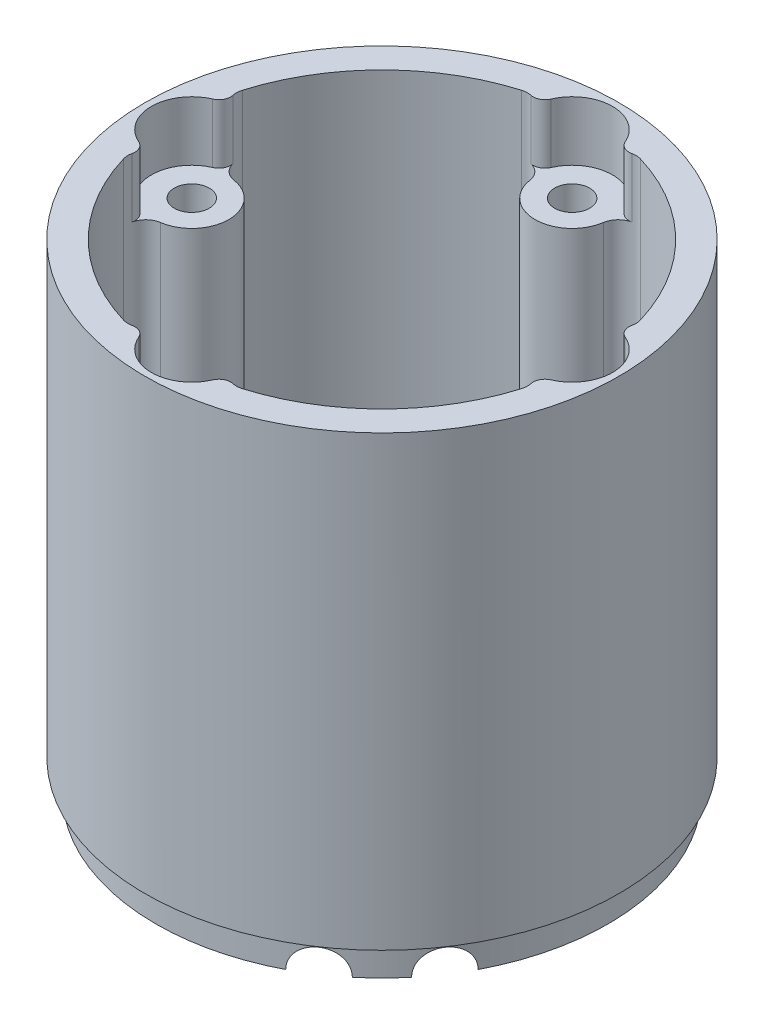
SolidWorks part; units mm, degrees
material "ABS"
ref_plane "Front Plane" through (0, 0, 0) normal (0, 0, 1) x (1, 0, 0)
ref_plane "Top Plane" through (0, 0, 0) normal (0, 1, 0) x (1, 0, 0)
ref_plane "Right Plane" through (0, 0, 0) normal (1, 0, 0) x (0, 0, -1)
sketch "Sketch1" plane through (0, 0, 0) normal (0, 0, 1) x (1, 0, 0)
  line L0 (0, 138.9318) -> (0, -74.0157) construction
  line L1 (44.45, 0) -> (44.45, 204.47)
  line L2 (44.45, 204.47) -> (50.7238, 204.47)
  line L3 (50.7238, 204.47) -> (50.7238, 108.585)
  line L4 (50.7238, 108.585) -> (52.832, 108.585)
  line L5 (52.832, 108.585) -> (52.832, 95.885)
  line L6 (52.832, 95.885) -> (50.7238, 95.885)
  line L7 (50.7238, 95.885) -> (50.7238, 0)
  line L8 (50.7238, 0) -> (44.45, 0)
  dimension "D1" = 88.9
  dimension "D2" = 204.47
  dimension "D3" = 12.7
  dimension "D4" = 101.4476
  dimension "D5" = 105.664
revolve "Revolve1" add sketch "Sketch1" angle 360 about L0
sketch "Sketch2" plane through (0, 204.47, 0) normal (0, 1, 0) x (1, 0, 0)
  circle A0 centre (0, 40.7035) radius 3.7465
  circle A1 centre (0, 0) radius 44.45 construction
  circle A2 centre (0, 40.7035) radius 7.9375
  circle A3 centre (0, 0) radius 50.8 construction
  point P26 (0, 0)
  dimension "D1" = 7.493
  dimension "D2" = 15.875
extrude "Boss-Extrude1" add sketch "Sketch2" against normal up to surface (204.47 mm away) up to face at (-50.7238, 0, 0)
fillet "Fillet1" radius 3.81 2 edges at (7.2879, 102.235, -43.8485) (-7.2879, 102.235, -43.8485)
pattern_circular "CirPattern1" count 4 over 360 about axis through (0, 138.9318, 0) along (0, 1, 0) of "Fillet1", "Boss-Extrude1" reverse direction yes
sketch "Sketch3" plane through (0, 204.47, 0) normal (0, 1, 0) x (1, 0, 0)
  circle A1 centre (0, 40.7035) radius 8.636
  dimension "D1" = 17.272
extrude "Cut-Extrude1" cut sketch "Sketch3" against normal blind 12.7
pattern_circular "CirPattern2" count 4 over 360 about axis through (0, 138.9318, 0) along (0, 1, 0) of "Cut-Extrude1" reverse direction yes
fillet "Fillet2" radius 2.54 8 edges at (-8.6158, 198.12, -41.2943) (8.6158, 198.12, -41.2943) (41.2943, 198.12, -8.6158) (41.2943, 198.12, 8.6158) (8.6158, 198.12, 41.2943) (-8.6158, 198.12, 41.2943) (-41.2943, 198.12, 8.6158) (-41.2943, 198.12, -8.6158)
ref_plane "Plane1" through (0, 102.235, 0) normal (0, 1, 0) x (1, 0, 0)
mirror "Mirror1" about plane through (0, 102.235, 0) normal (0, 1, 0) of "CirPattern2"
fillet "Fillet3" radius 2.54 8 edges at (-41.2943, 6.35, -8.6158) (-41.2943, 6.35, 8.6158) (8.6158, 6.35, 41.2943) (-8.6158, 6.35, 41.2943) (41.2943, 6.35, -8.6158) (41.2943, 6.35, 8.6158) (-8.6158, 6.35, -41.2943) (8.6158, 6.35, -41.2943)
chamfer "Chamfer1" distance 1.27 angle 80 1 edges at (-50.7238, 95.885, 0) first distance on face at (-50.7238, 95.885, 0)
ref_plane "Plane2" through (37.3579, 0, 37.3579) normal (0.7071, 0, 0.7071) x (0, 1, 0)
hole_wizard "3/8 Clearance Hole1" positions "Sketch6" profile "Sketch5" hole size "3/8" standard "ANSI Inch"
sketch "Sketch6" plane through (37.3579, 0, 37.3579) normal (0.7071, 0, 0.7071) x (0, 1, 0)
  line L1 (94.9867, 0) -> (108.585, 0)
  line L2 (94.9867, 52.832) -> (94.9867, -52.832) construction
  line L3 (108.585, -50.7238) -> (108.585, 50.7238) construction
  line L5 (101.7859, 9.525) -> (101.7859, -9.525)
  point P0 (101.7859, -9.525)
  point P2 (101.7859, 9.525)
  point P36 (101.7859, 0)
  point P40 (101.7859, 0)
  dimension "D1" = 19.05
sketch "Sketch5" plane through (44.0931, 101.7859, 30.6227) normal (0, 1, 0) x (0.7071, 0, -0.7071)
  line L0 (0, 0) -> (0, 57.8935)
  line L1 (0, 57.8935) -> (5.0419, 54.864)
  line L2 (5.0419, 54.864) -> (5.0419, 0)
  line L5 (5.0419, 0) -> (0, 0)
  line L10 (0, 57.8935) -> (-5.0419, 54.864) construction
  line L11 (0, -6.35) -> (0, 107.95) construction
  dimension "Hole Dia." = 10.0838
  dimension "Hole Depth" = 54.864
  dimension "Drill Angle" = 118
ref_plane "Plane3" through (37.3579, 0, -37.3579) normal (0.7071, 0, -0.7071) x (0, 1, 0)
hole_wizard "#6 Clearance Hole1" positions "Sketch7" profile "Sketch8" hole size "#6" standard "ANSI Inch"
sketch "Sketch7" plane through (37.3579, 0, -37.3579) normal (0.7071, 0, -0.7071) x (0, 1, 0)
  line L2 (94.9867, 0) -> (108.585, 0)
  line L3 (94.9867, 52.832) -> (94.9867, -52.832) construction
  line L4 (108.585, -52.832) -> (108.585, 52.832) construction
  point P0 (101.7859, 0)
  point P21 (101.7859, 0)
sketch "Sketch8" plane through (37.3579, 101.7859, -37.3579) normal (0, 1, 0) x (-0.7071, 0, -0.7071)
  line L0 (0, 0) -> (0, 56.0048)
  line L1 (0, 56.0048) -> (1.8986, 54.864)
  line L2 (1.8986, 54.864) -> (1.8986, 0)
  line L5 (1.8986, 0) -> (0, 0)
  line L10 (0, 56.0048) -> (-1.8987, 54.864) construction
  line L11 (0, -6.35) -> (0, 107.95) construction
  dimension "Hole Dia." = 3.7973
  dimension "Hole Depth" = 54.864
  dimension "Drill Angle" = 118
pattern_circular "CirPattern3" count 3 every 90 about axis through (0, 138.9318, 0) along (0, 1, 0) of "#6 Clearance Hole1"
sketch "Sketch9" plane through (0, 204.47, 0) normal (0, 1, 0) x (1, 0, 0)
  circle A0 centre (0, 0) radius 52.832
extrude "Cut-Extrude2" cut sketch "Sketch9" along normal blind 101.7881 from surface starting at face at (0, 0, 0)
sketch "Sketch10" plane through (0, 0, 0) normal (0, 0, 1) x (1, 0, 0)
  line L0 (0, 204.47) -> (0, 101.7881) construction
  line L1 (50.7238, 204.47) -> (-50.7238, 204.47) construction
  line L2 (-52.832, 101.7881) -> (52.832, 101.7881) construction
  line L4 (52.832, 108.585) -> (48.387, 108.585)
  line L5 (52.832, 108.585) -> (52.832, 101.7881)
  line L6 (52.832, 101.7881) -> (48.387, 101.7881)
  line L7 (48.387, 108.585) -> (48.387, 101.7881)
  dimension "D1" = 4.445
revolve "Cut-Revolve1" cut sketch "Sketch10" angle 360 about L0
